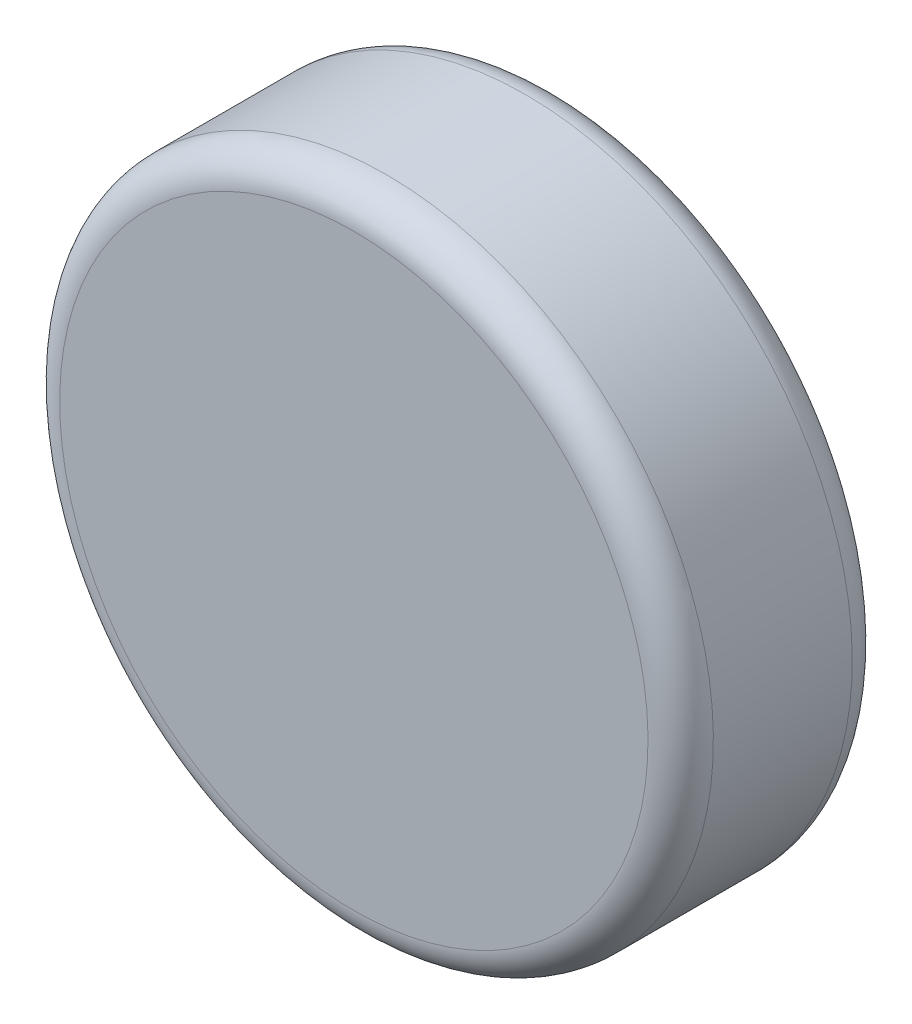
SolidWorks part; units mm, degrees
ref_plane "Front Plane" through (0, 0, 0) normal (0, 0, 1) x (1, 0, 0)
ref_plane "Top Plane" through (0, 0, 0) normal (0, 1, 0) x (1, 0, 0)
ref_plane "Right Plane" through (0, 0, 0) normal (1, 0, 0) x (0, 0, -1)
sketch "Sketch1" plane through (0, 0, 15.895) normal (0, 0, -1) x (-1, 0, 0)
  circle A0 centre (4.95, -15.4) radius 4 construction
  circle A1 centre (4.95, -15.4) radius 4
extrude "Boss-Extrude1" add sketch "Sketch1" along normal blind 2.5
fillet "Fillet1" radius 0.4 2 edges at (-4.95, -11.4, 15.895) (-4.95, -11.4, 13.395)
